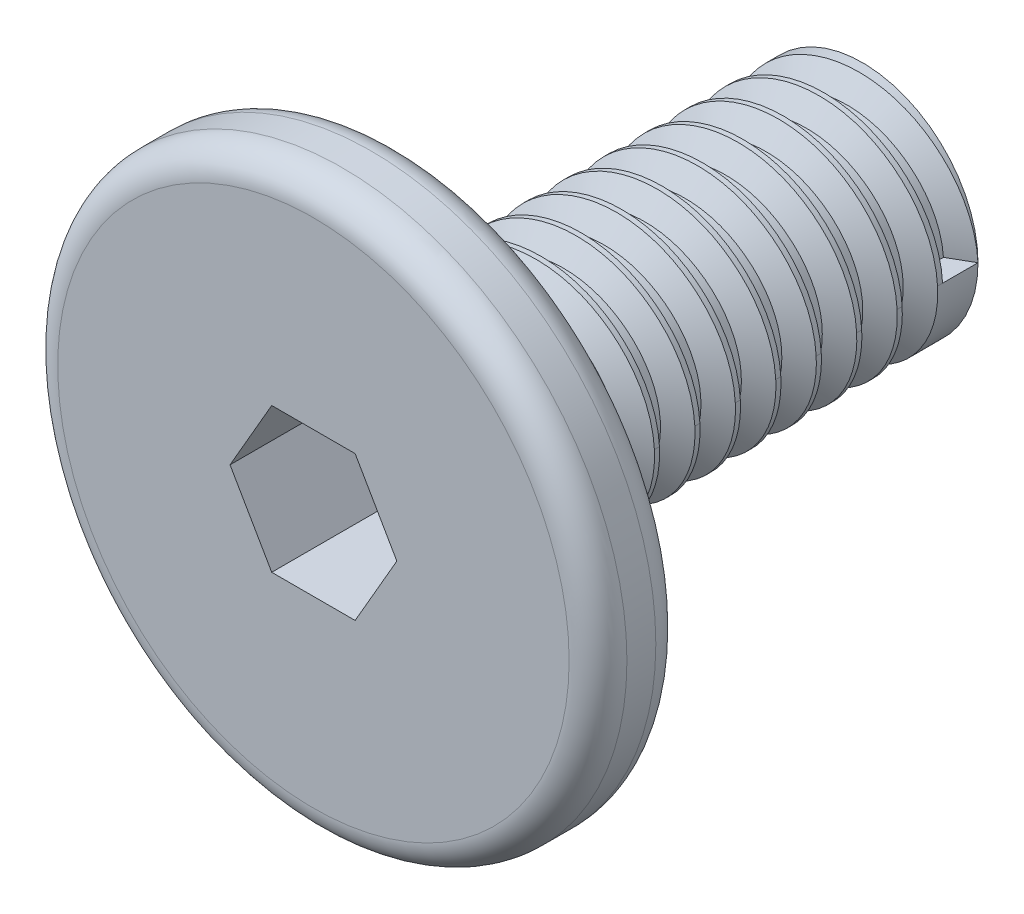
SolidWorks part; units mm, degrees
ref_plane "Спереди" through (0, 0, 0) normal (0, 0, 1) x (1, 0, 0)
ref_plane "Сверху" through (0, 0, 0) normal (0, 1, 0) x (1, 0, 0)
ref_plane "Справа" through (0, 0, 0) normal (1, 0, 0) x (0, 0, -1)
sketch "Эскиз1" plane through (0, 0, 0) normal (0, 0, 1) x (1, 0, 0)
  circle A0 centre (0, 0) radius 4.925
  dimension "D1" = 9.85
extrude "Бобышка-Вытянуть1" add sketch "Эскиз1" along normal blind 1.5
sketch "Эскиз2" plane through (0, 0, 0) normal (0, 0, -1) x (-1, 0, 0)
  circle A0 centre (0, 0) radius 2
  dimension "D1" = 4
extrude "Бобышка-Вытянуть2" add sketch "Эскиз2" along normal blind 8
thread "Резьба1" pitch 0.7 method cut profile "Профиль резьбы1" start angle 0, offset 0, length 7, pitch 0.7, diameter 4
ref_plane "Плоскость1" through (2, 0, -8) normal (0, -1, 0) x (1, 0, 0)
sketch "Профиль резьбы1" plane through (2, 0, -8) normal (0, -1, 0) x (1, 0, 0)
  line L0 (0, 0) -> (0, 0.7) construction
  line L11 (0, 0) -> (0, 0.6125)
  line L12 (0, 0.6125) -> (-0.3789, 0.3937)
  line L13 (-0.3789, 0.3937) -> (-0.3789, 0.2187)
  line L15 (-0.3789, 0.2187) -> (0, 0)
  line L17 (-0.3789, 0.3062) -> (0, 0.3062) construction
  point P2 (0, 0)
  dimension "Pitch" = 0.7
  dimension "Profile_Angle" = 60
  dimension "Profile_Land" = 0.175
  dimension "Profile_Height" = 0.3789
sketch "Эскиз5" plane through (0, 0, 1.5) normal (0, 0, 1) x (1, 0, 0)
  line L1 (0.7217, -1.25) -> (1.4434, 0)
  line L2 (1.4434, 0) -> (0.7217, 1.25)
  line L3 (0.7217, 1.25) -> (-0.7217, 1.25)
  line L4 (-0.7217, 1.25) -> (-1.4434, 0)
  line L5 (-1.4434, 0) -> (-0.7217, -1.25)
  line L6 (-0.7217, -1.25) -> (0.7217, -1.25)
  circle A0 centre (0, 0) radius 1.25 construction
  dimension "D1" = 2.5
extrude "Вырез-Вытянуть1" cut sketch "Эскиз5" against normal blind 2
fillet "Скругление1" radius 0.5 2 edges at (4.925, 0, 0) (4.925, 0, 1.5)
